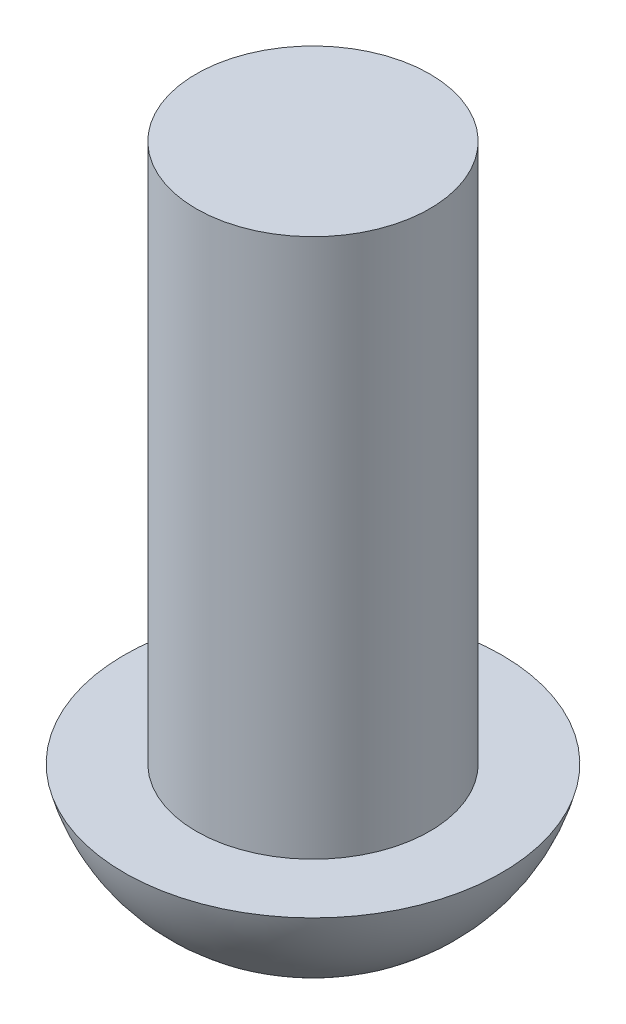
SolidWorks part; units mm, degrees
ref_plane "Front Plane" through (0, 0, 0) normal (0, 0, 1) x (1, 0, 0)
ref_plane "Top Plane" through (0, 0, 0) normal (0, 1, 0) x (1, 0, 0)
ref_plane "Right Plane" through (0, 0, 0) normal (1, 0, 0) x (0, 0, -1)
sketch "Sketch1" plane through (0, 0, 0) normal (0, 1, 0) x (1, 0, 0)
  circle A0 centre (0, 0) radius 1.3
  dimension "D1" = 2.6
extrude "Boss-Extrude1" add sketch "Sketch1" along normal blind 6 contours A0
sketch "Sketch2" plane through (0, 0, 0) normal (0, -1, 0) x (1, 0, 0)
  circle A0 centre (0, 0) radius 2.1
  circle A1 centre (0, 0) radius 1.3 construction
  circle A2 centre (0, 0) radius 1.3 construction
  dimension "D1" = 4.2
extrude "Boss-Extrude2" add sketch "Sketch2" along normal blind 1.5
fillet "Fillet1" radius 2 1 edges at (0, -1.5, -2.1)
sketch "Sketch3" plane through (0, -1.5, 0) normal (0, -1, 0) x (1, 0, 0)
  line L0 (0.375, 0.375) -> (1.5, 0.375)
  line L1 (-0.375, -1.5) -> (0.375, -1.5)
  line L2 (-0.375, -1.5) -> (-0.375, -0.375)
  line L3 (-0.375, 1.5) -> (0.375, 1.5)
  line L4 (0.375, -1.5) -> (0.375, -0.375)
  line L7 (-1.5, -0.375) -> (-0.375, -0.375)
  line L8 (-1.5, -0.375) -> (-1.5, 0.375)
  line L9 (-1.5, 0.375) -> (-0.375, 0.375)
  line L10 (1.5, -0.375) -> (1.5, 0.375)
  line L15 (0.375, 0.375) -> (0.375, 1.5)
  line L16 (0.375, -0.375) -> (1.5, -0.375)
  line L17 (-0.375, 0.375) -> (-0.375, 1.5)
  point P0 (0, 0)
  point P6 (0, 0)
  dimension "D1" = 3
  dimension "D2" = 0.75
extrude "Cut-Extrude1" cut sketch "Sketch3" against normal blind 1 draft 15
sketch "Sketch5" [suppressed] plane through (0, 0, 0) normal (0, 0, 1) x (1, 0, 0)
  line L0 (-2.1, -2) -> (2.1, -2) construction
  line L3 (0, 0) -> (0, 24) construction
  point P6 (0, 11)
  dimension "D1" = 13
  dimension "D2" = 26
sketch "Sketch6" [suppressed] plane through (0, 0, 0) normal (0, 0, 1) x (1, 0, 0)
  line L0 (0, 0) -> (0, 70) construction
  line L1 (4, 70) -> (-4, 70) construction
